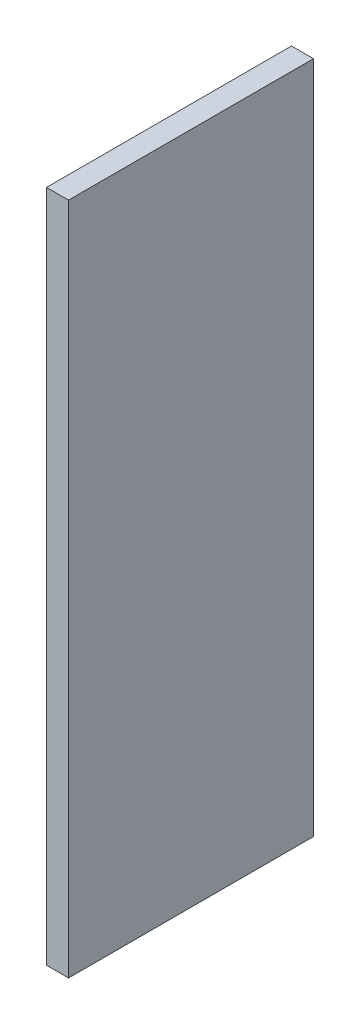
SolidWorks part; units mm, degrees
ref_plane "Front Plane" through (0, 0, 0) normal (0, 0, 1) x (1, 0, 0)
ref_plane "Top Plane" through (0, 0, 0) normal (0, 1, 0) x (1, 0, 0)
ref_plane "Right Plane" through (0, 0, 0) normal (1, 0, 0) x (0, 0, -1)
sketch "Sketch1" plane through (0, 0, 0) normal (1, 0, 0) x (0, 0, -1)
  line L1 (-30.4666, 510.8196) -> (172.7334, 510.8196)
  line L2 (-30.4666, 510.8196) -> (-30.4666, -47.9804)
  line L3 (-30.4666, -47.9804) -> (172.7334, -47.9804)
  line L4 (172.7334, 510.8196) -> (172.7334, -47.9804)
extrude "Boss-Extrude1" add sketch "Sketch1" along normal blind 18.2562 contours L2 L1 L4 L3
